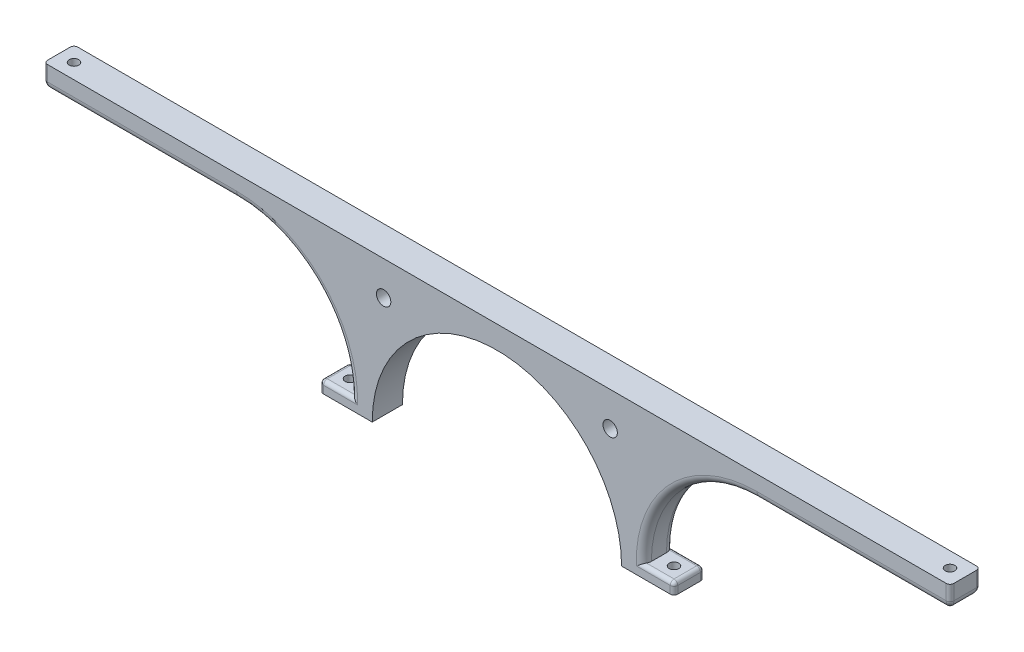
SolidWorks part; units mm, degrees
ref_plane "Front Plane" through (0, 0, 0) normal (0, 0, 1) x (1, 0, 0)
ref_plane "Top Plane" through (0, 0, 0) normal (0, 1, 0) x (1, 0, 0)
ref_plane "Right Plane" through (0, 0, 0) normal (1, 0, 0) x (0, 0, -1)
sketch "Sketch1" plane through (0, 0, 0) normal (0, 0, 1) x (1, 0, 0)
  line L0 (-97.55, 0) -> (-117.2613, 0)
  line L1 (-300, 97.55) -> (300, 97.55)
  line L2 (-300, 97.55) -> (-300, 82.55)
  line L3 (-300, 82.55) -> (-172.3113, 82.55)
  line L4 (300, 97.55) -> (300, 82.55)
  line L5 (300, 82.55) -> (172.3113, 82.55)
  line L6 (-117.2613, 0) -> (-117.2613, 7.5)
  line L7 (-117.2613, 7.5) -> (-97.2613, 7.5)
  line L8 (97.55, 0) -> (117.2613, 0)
  line L9 (117.2613, 0) -> (117.2613, 7.5)
  line L10 (117.2613, 7.5) -> (97.2613, 7.5)
  line L11 (-97.2613, 7.5) -> (-172.3113, 7.5) construction
  line L12 (0, 97.55) -> (0, -97.55) construction
  line L13 (-97.55, 0) -> (-82.55, 0)
  line L14 (82.55, 0) -> (97.6369, 0)
  arc A0 (82.55, 0) -> (-82.55, 0) centre (0, 0) ccw
  arc A6 (97.2613, 7.5) -> (172.3113, 82.55) centre (172.3113, 7.5) cw
  circle A7 centre (-75, 75) radius 4.7625
  arc A9 (-97.2613, 7.5) -> (-172.3113, 82.55) centre (-172.3113, 7.5) ccw
  circle A10 centre (75, 75) radius 4.7625
  point P8 (0, 0)
  point P11 (0, 97.55)
  dimension "D1" = 165.1
  dimension "D7" = 600
  dimension "D11" = 9.525
  dimension "D3" = 20
  dimension "D4" = 20
  dimension "D5" = 7.5
  dimension "D6" = 75.05
  dimension "D2" = 97.2613
  dimension "D9" = 97.2613
  dimension "D10" = 97.55
  dimension "D12" = 75
  dimension "D13" = 75
extrude "Boss-Extrude1" add sketch "Sketch1" along normal blind 20 contours A9 L7 L6 L0 L13 A0 L14 L8 L9 L10 A6 L5 L4 L1 L2 L3 A7 A10 region at (-107.4056, 6.0788, 0)
sketch "Sketch2" plane through (0, 0, 0) normal (0, -1, 0) x (1, 0, 0)
  line L0 (0, 0) -> (0, 78.7828) construction
  line L1 (117.2613, 20) -> (117.2613, 0) construction
  line L2 (82.55, 20) -> (117.2613, 20) construction
  circle A0 centre (107.2613, 10) radius 3.175
  circle A1 centre (-107.2613, 10) radius 3.175
  point P7 (117.2613, 10)
  dimension "D1" = 6.35
  dimension "D2" = 10
  dimension "D3" = 10
extrude "Cut-Extrude1" cut sketch "Sketch2" against normal up to next
fillet "Fillet4" radius 5 10 edges at (-236.1556, 82.55, 20) (-236.1556, 82.55, 0) (236.1556, 82.55, 0) (236.1556, 82.55, 20) (300, 82.55, 10) (-300, 82.55, 10) (-119.2429, 60.5684, 20) (-119.2429, 60.5684, 0) (119.2429, 60.5684, 0) (119.2429, 60.5684, 20)
fillet "Fillet5" radius 2.5 18 edges at (-117.2613, 3.75, 0) (117.2613, 3.75, 0) (117.2613, 3.75, 20) (-117.2613, 3.75, 20) (-104.7613, 7.5, 20) (-117.2613, 7.5, 10) (-104.7613, 7.5, 0) (117.2613, 7.5, 10) (104.7613, 7.5, 0) (104.7613, 7.5, 20) (-298.5355, 84.0145, 18.5355) (-298.5355, 84.0145, 1.4645) (298.5355, 84.0145, 1.4645) (298.5355, 84.0145, 18.5355) (-300, 92.55, 20) (-300, 92.55, 0) (300, 92.55, 0) (300, 92.55, 20)
sketch "Sketch3" plane through (0, 97.55, 0) normal (0, 1, 0) x (1, 0, 0)
  line L0 (0, 0) -> (0, 36.8027) construction
  line L1 (300, -17.5) -> (300, -2.5) construction
  line L2 (-297.5, 0) -> (297.5, 0) construction
  circle A0 centre (290, -10) radius 3.175
  circle A1 centre (-290, -10) radius 3.175
  dimension "D1" = 6.35
  dimension "D2" = 10
  dimension "D3" = 10
extrude "Cut-Extrude2" cut sketch "Sketch3" against normal up to next
